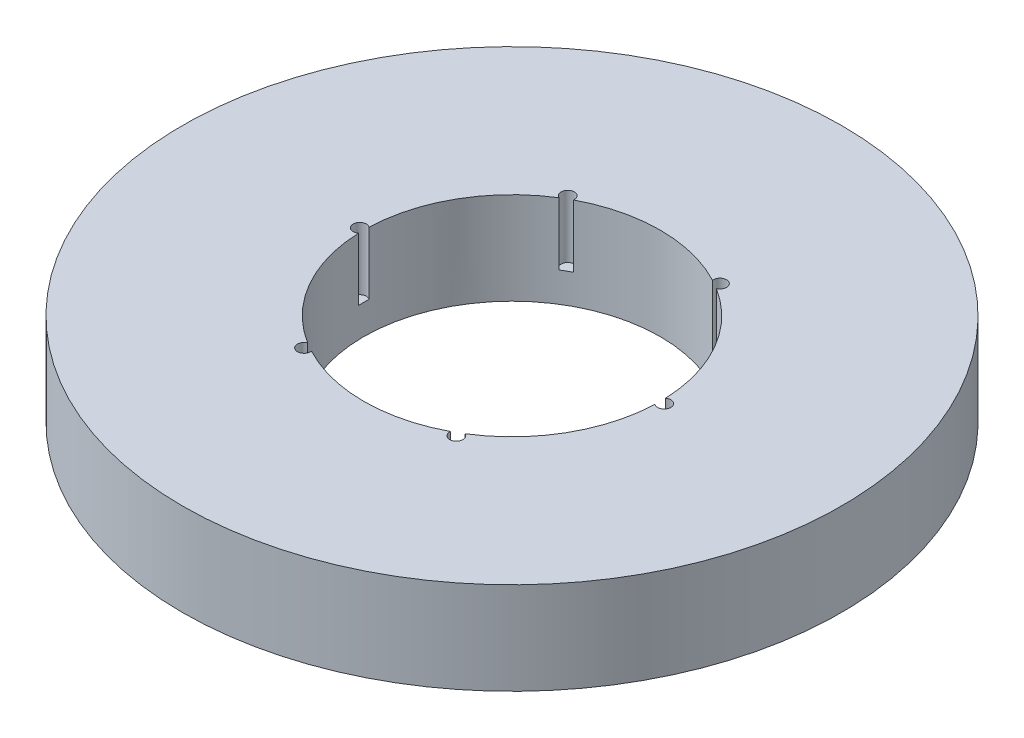
SolidWorks part; units mm, degrees
ref_plane "Front Plane" through (0, 0, 0) normal (0, 0, 1) x (1, 0, 0)
ref_plane "Top Plane" through (0, 0, 0) normal (0, 1, 0) x (1, 0, 0)
ref_plane "Right Plane" through (0, 0, 0) normal (1, 0, 0) x (0, 0, -1)
sketch "Sketch1" plane through (0, 0, 0) normal (0, 1, 0) x (1, 0, 0)
  circle A0 centre (0, 0) radius 100
  dimension "FLANGE_OD" = 200
extrude "Boss-Extrude1" add sketch "Sketch1" along normal blind 28
sketch "Sketch2" plane through (0, 0, 0) normal (0, 1, 0) x (1, 0, 0)
  circle A0 centre (0, 0) radius 45
  dimension "BORE_D" = 90
extrude "Cut-Extrude1" cut sketch "Sketch2" along normal through all
sketch "Sketch3" plane through (0, 28, 0) normal (0, 1, 0) x (1, 0, 0)
  circle A0 centre (0, 0) radius 46.1944 construction
  circle A1 centre (-46.1944, 0) radius 2.0106
  dimension "BOLT_D" = 4.0212
  dimension "BOLT_PCD" = 92.3887
extrude "Cut-Extrude2" cut sketch "Sketch3" against normal blind 18.9925
pattern_circular "CirPattern1" count 6 over 360 about axis through (0, 0, 0) along (0, 1, 0) of "Cut-Extrude2"
